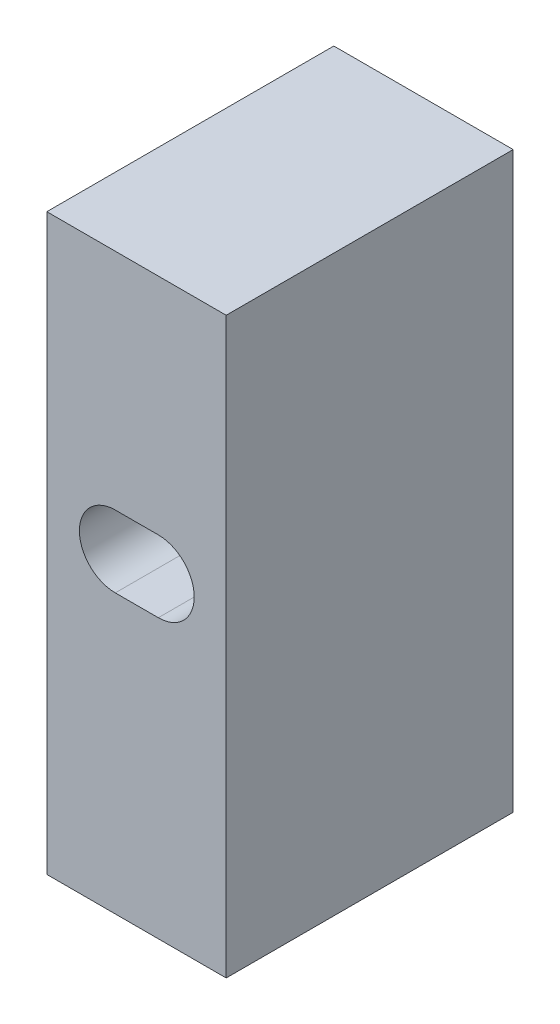
SolidWorks part; units mm, degrees
ref_plane "Front Plane" through (0, 0, 0) normal (0, 0, 1) x (1, 0, 0)
ref_plane "Top Plane" through (0, 0, 0) normal (0, 1, 0) x (1, 0, 0)
ref_plane "Right Plane" through (0, 0, 0) normal (1, 0, 0) x (0, 0, -1)
sketch "Sketch1" plane through (0, 0, 0) normal (0, 1, 0) x (1, 0, 0)
  line L1 (0, 0) -> (15.875, 0)
  line L2 (0, 0) -> (0, 25.4)
  line L3 (0, 25.4) -> (15.875, 25.4)
  line L4 (15.875, 0) -> (15.875, 25.4)
  dimension "D1" = 15.875
  dimension "D2" = 25.4
extrude "Boss-Extrude1" add sketch "Sketch1" along normal blind 50.8
hole_wizard "Tap Drill for #10-24 Tap1" positions "Sketch3" profile "Sketch4" hole size "#10-24" standard "ANSI Inch"
sketch "Sketch3" plane through (0, 0, 0) normal (0, -1, 0) x (-1, 0, 0)
  line L1 (0, 0) -> (-15.875, 0) construction
  line L2 (-15.875, 25.4) -> (0, 25.4) construction
  point P8 (-7.9375, 6)
  point P10 (-7.9375, 19.4)
  point P14 (-7.9375, 0)
  point P17 (-7.9375, 25.4)
  dimension "D1" = 6
  dimension "D2" = 6
sketch "Sketch4" plane through (7.9375, 0, -6) normal (1, 0, 0) x (0, 0, -1)
  line L0 (0, 0) -> (0, 21.8418)
  line L1 (0, 21.8418) -> (1.8986, 20.701)
  line L2 (1.8986, 20.701) -> (1.8986, 0)
  line L5 (1.8986, 0) -> (0, 0)
  line L10 (0, 21.8418) -> (-1.8987, 20.701) construction
  line L11 (0, -6.35) -> (0, 107.95) construction
  dimension "Hole Dia." = 3.7973
  dimension "Hole Depth" = 20.701
  dimension "Drill Angle" = 118
hole_wizard "Tap Drill Slot for #10-24 Tap1" positions "Sketch5" profile "Sketch6" size "#10-24" standard "ANSI Inch" slot yes end condition through all
sketch "Sketch5" plane through (-765.9907, -1161.9308, 0) normal (0, 0, 1) x (1, 0, 0)
  line L0 (768.8745, 1189.7184) -> (779.0345, 1189.7184) construction
  point P0 (773.9545, 1189.7184)
sketch "Sketch6" plane through (7.9638, 27.7876, 0) normal (1, 0, 0) x (0, -1, 0)
  line L0 (0, 0) -> (0, 25.4)
  line L1 (0, 25.4) -> (3.175, 25.4)
  line L2 (3.175, 25.4) -> (3.175, 0)
  line L3 (3.175, 0) -> (0, 0)
  line L4 (0, -6.35) -> (0, 107.95) construction
  dimension "Thru Hole Dia." = 6.35
  dimension "Thru Hole Depth" = 25.4
